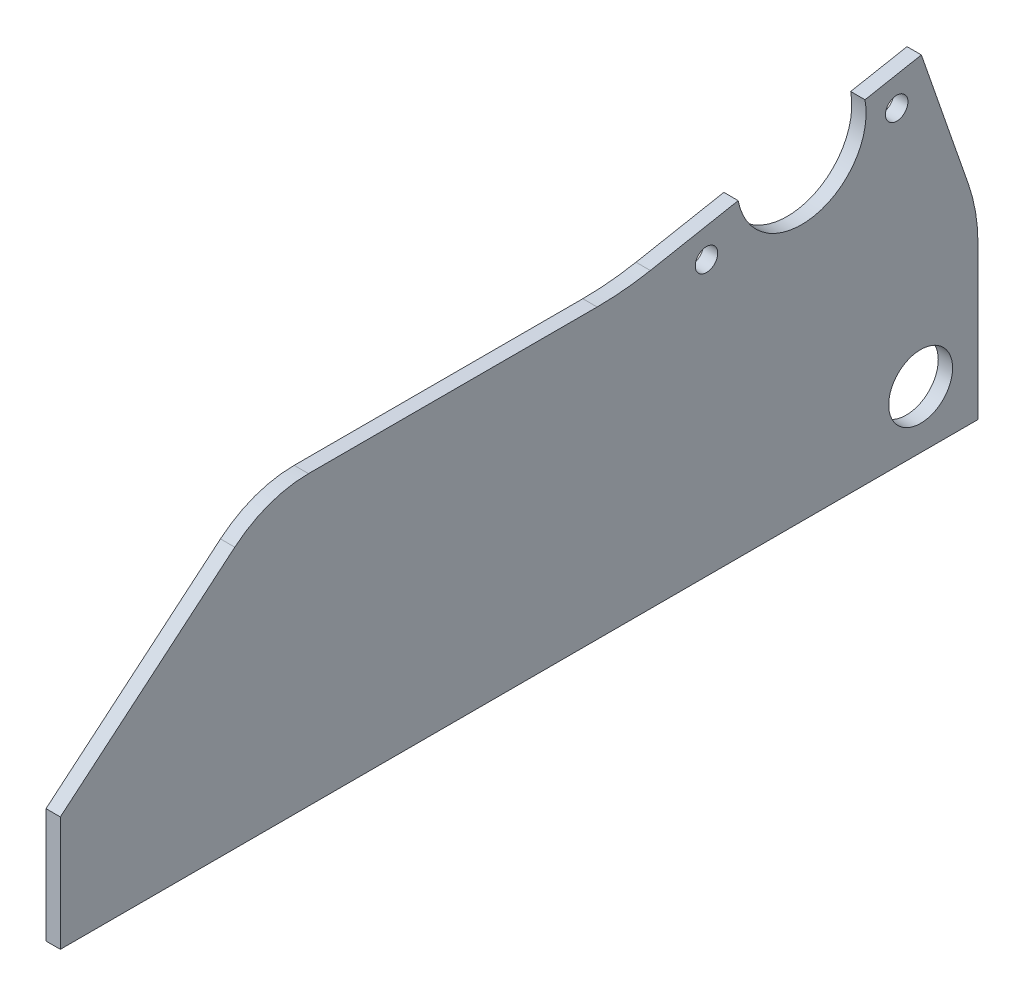
SolidWorks part; units mm, degrees
material "6061 Alloy"
ref_plane "Front Plane" through (0, 0, 0) normal (0, 0, 1) x (1, 0, 0)
ref_plane "Top Plane" through (0, 0, 0) normal (0, 1, 0) x (1, 0, 0)
ref_plane "Right Plane" through (0, 0, 0) normal (1, 0, 0) x (0, 0, -1)
sketch "Sketch1" plane through (0, 0, 0) normal (1, 0, 0) x (0, 0, -1)
  line L0 (0, -38.1) -> (0, 1.9909)
  line L7 (-12.543, 38.1) -> (-25.0221, 35.7419)
  line L8 (-53.1002, 30.4361) -> (-78.3936, 25.6566)
  line L10 (-78.3936, 25.6566) -> (-148.2436, 25.6566)
  line L13 (-203.2, -38.1) -> (0, -38.1)
  line L14 (-203.2, -38.1) -> (-203.2, -12.7)
  line L15 (-203.2, -12.7) -> (-164.5704, 19.7141)
  line L16 (-203.2, -12.7) -> (0, -12.7) construction
  line L17 (-12.543, 38.1) -> (0, 1.9909)
  arc A2 (-25.0221, 35.7419) -> (-53.1002, 30.4361) centre (-39.0612, 33.089) cw
  arc A4 (-148.2436, 25.6566) -> (-164.5704, 19.7141) centre (-148.2436, 0.2566) ccw
  point P4 (0, 0)
  dimension "D1" = 28.575
  dimension "D4" = 25.4
  dimension "D7" = 25.4
  dimension "D2" = 76.2
  dimension "D6" = 203.2
  dimension "D8" = 50
  dimension "D9" = 69.85
extrude "Boss-Extrude1" add sketch "Sketch1" along normal blind 3.175
hole_wizard "#10 Clearance Hole1" positions "Sketch2" profile "Sketch3" hole size "#10" standard "ANSI Inch" end condition through all
sketch "Sketch2" plane through (3.175, 0, 0) normal (1, 0, 0) x (0, 0, -1)
  line L0 (-53.1002, 30.4361) -> (-78.3936, 25.6566) construction
  line L1 (-60.1197, 22.6473) -> (-18.0026, 30.6059) construction
  line L3 (-39.0612, 26.6266) -> (-39.0612, 33.089) construction
  line L4 (-12.543, 38.1) -> (-25.0221, 35.7419) construction
  point P0 (-60.1197, 22.6473)
  point P2 (-18.0026, 30.6059)
  dimension "D1" = 42.8625
  dimension "D2" = 6.35
sketch "Sketch3" plane through (3.175, 22.6473, 60.1197) normal (0, 1, 0) x (0, 0, -1)
  line L0 (0, 0) -> (0, 3.175)
  line L1 (0, 3.175) -> (2.4892, 3.175)
  line L2 (2.4892, 3.175) -> (2.4892, 0)
  line L5 (2.4892, 0) -> (0, 0)
  line L11 (0, -6.35) -> (0, 107.95) construction
  dimension "Thru Hole Dia." = 4.9784
  dimension "Thru Hole Depth" = 3.175
sketch "Sketch9" plane through (3.175, 0, 0) normal (1, 0, 0) x (0, 0, -1)
  line L2 (0, -38.1) -> (0, 1.9909) construction
  line L3 (-203.2, -38.1) -> (0, -38.1) construction
  circle A0 centre (-12.7, -25.4) radius 7.0739
  dimension "D1" = 14.1478
  dimension "D3" = 12.7
  dimension "D2" = 12.7
extrude "Cut-Extrude1" cut sketch "Sketch9" against normal through all
fillet "Fillet1" radius 38.1 1 edges at (1.5875, 1.9909, 0)
fillet "Fillet2" radius 63.5 1 edges at (1.5875, 25.6566, 78.3936)
